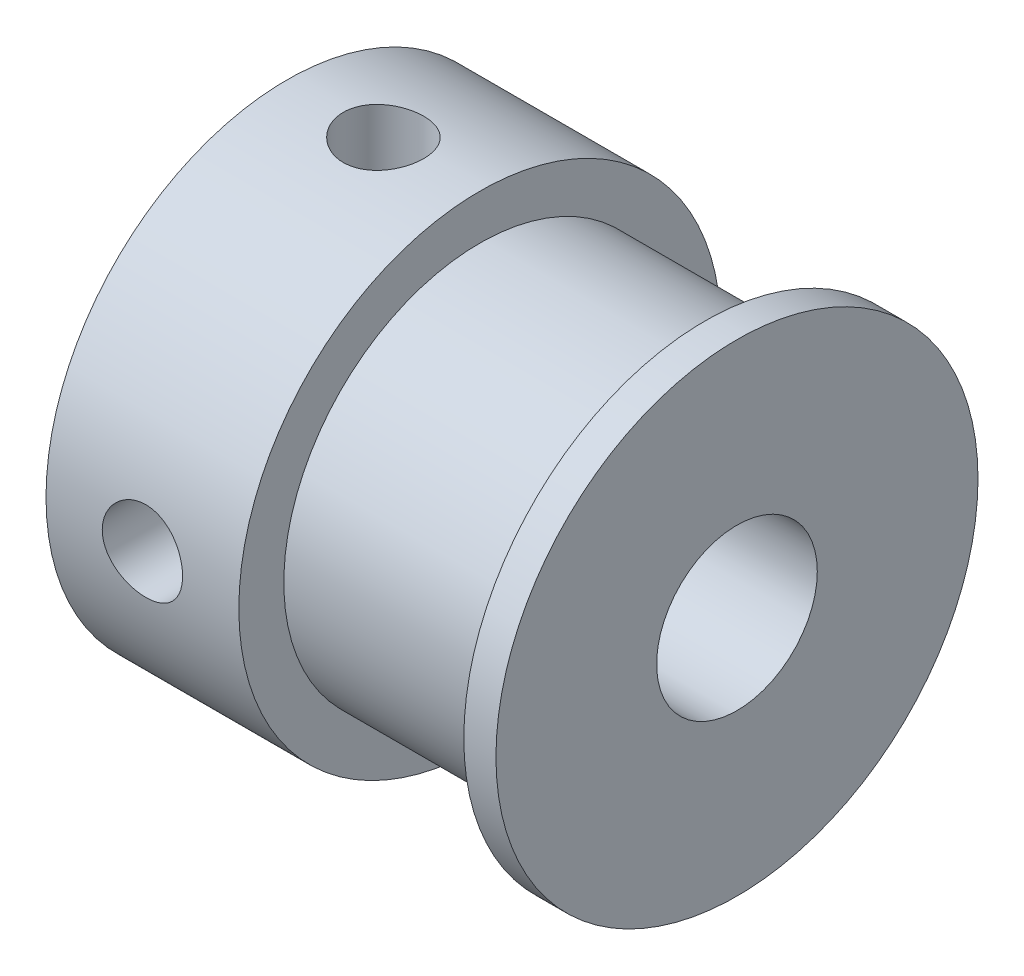
SolidWorks part; units mm, degrees
material "6061-T6 (SS)"
ref_plane "Front Plane" through (0, 0, 0) normal (0, 0, 1) x (1, 0, 0)
ref_plane "Top Plane" through (0, 0, 0) normal (0, 1, 0) x (1, 0, 0)
ref_plane "Right Plane" through (0, 0, 0) normal (1, 0, 0) x (0, 0, -1)
sketch "Sketch1" plane through (0, 0, 0) normal (0, 0, 1) x (1, 0, 0)
  line L0 (0, 2.5) -> (0, 7.5)
  line L1 (0, 7.5) -> (6, 7.5)
  line L2 (6, 7.5) -> (6, 6.1)
  line L3 (6, 6.1) -> (13, 6.1)
  line L4 (13, 6.1) -> (13, 7.5)
  line L5 (13, 7.5) -> (14, 7.5)
  line L6 (14, 7.5) -> (14, 2.5)
  line L7 (14, 2.5) -> (0, 2.5)
  line L8 (0, 0) -> (-7.6744, 0) construction
  dimension "D1" = 5
  dimension "D2" = 15
  dimension "D3" = 12.2
  dimension "D4" = 6
  dimension "D5" = 14
  dimension "D6" = 1
revolve "Revolve1" add sketch "Sketch1" angle 360 about L8
hole_wizard "M3x0.5 Tapped Hole1" positions "Sketch3" profile "Sketch2" tap size "M3x0.5" standard "ANSI Metric" end condition through all
sketch "Sketch3" plane through (0, 0, 0) normal (0, 1, 0) x (1, 0, 0)
  line L0 (0, 0) -> (6, 0) construction
  line L1 (6, -6.1) -> (6, 6.1) construction
  point P8 (3, 0)
sketch "Sketch2" plane through (3, 0, 0) normal (1, 0, 0) x (0, 0, -1)
  line L0 (0, 0) -> (0, 7.5)
  line L1 (0, 7.5) -> (1.25, 7.5)
  line L2 (1.25, 7.5) -> (1.25, 0)
  line L5 (1.25, 0) -> (0, 0)
  line L11 (0, -6.35) -> (0, 107.95) construction
  dimension "Thread Major Dia." = 2.5
  dimension "Thru Tap Drill Depth" = 7.5
hole_wizard "M3x0.5 Tapped Hole2" positions "Sketch5" profile "Sketch4" tap size "M3x0.5" standard "ANSI Metric" end condition through all
sketch "Sketch5" plane through (0, 0, 0) normal (0, 0, 1) x (1, 0, 0)
  line L0 (0, 0) -> (6, 0) construction
  line L1 (6, -6.1) -> (6, 6.1) construction
  point P7 (3, 0)
sketch "Sketch4" plane through (3, 0, 0) normal (1, 0, 0) x (0, 1, 0)
  line L0 (0, 0) -> (0, 7.5)
  line L1 (0, 7.5) -> (1.25, 7.5)
  line L2 (1.25, 7.5) -> (1.25, 0)
  line L5 (1.25, 0) -> (0, 0)
  line L11 (0, -6.35) -> (0, 107.95) construction
  dimension "Thread Major Dia." = 2.5
  dimension "Thru Tap Drill Depth" = 7.5
